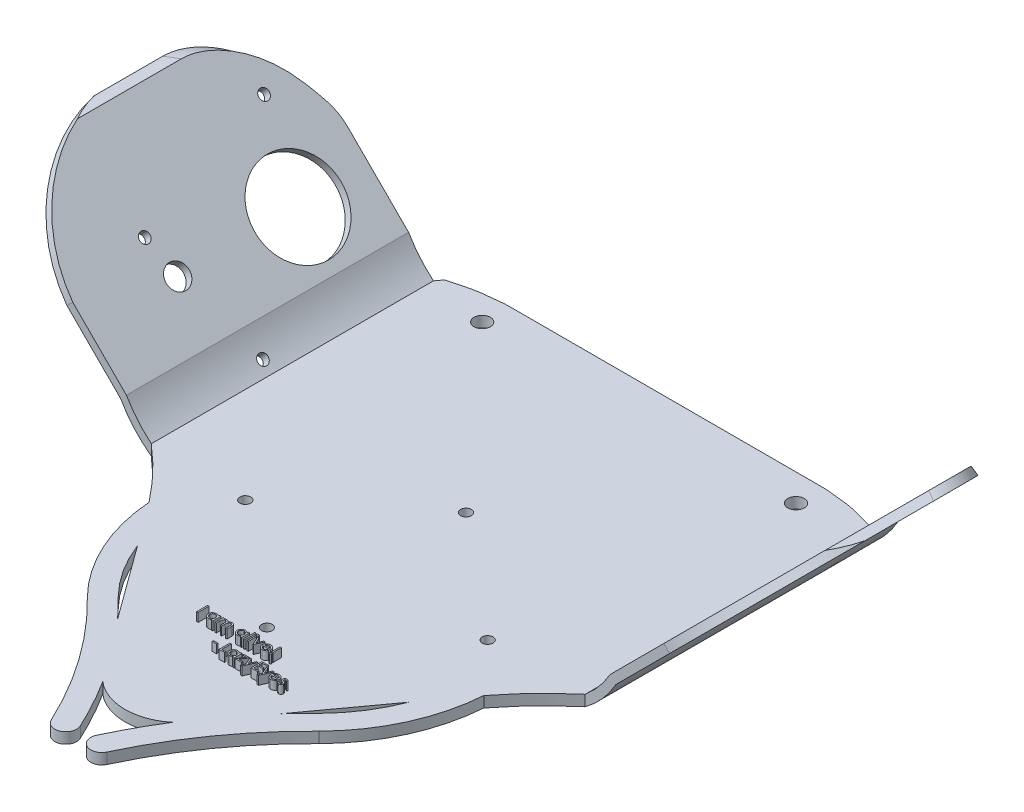
SolidWorks part; units mm, degrees
ref_plane "Front Plane" through (0, 0, 0) normal (0, 0, 1) x (1, 0, 0)
ref_plane "Top Plane" through (0, 0, 0) normal (0, 1, 0) x (1, 0, 0)
ref_plane "Right Plane" through (0, 0, 0) normal (1, 0, 0) x (0, 0, -1)
sketch "Sketch1" plane through (0, 0, 0) normal (0, 1, 0) x (1, 0, 0)
  line L0 (-53.9242, 189.7484) -> (-47.5742, 190.4453)
  line L1 (47.5742, 190.4453) -> (53.9242, 189.7484)
  line L2 (-63.6671, 185.8801) -> (-63.6671, 115.569)
  line L3 (63.6671, 185.8801) -> (63.6671, 115.569)
  line L4 (-63.6671, 115.569) -> (-63.6671, 103.057)
  line L5 (-62.2755, 187.7215) -> (-58.366, 188.769)
  line L6 (-63.6671, 185.8801) -> (-62.2755, 187.7215)
  line L7 (63.6671, 115.569) -> (63.6671, 103.057)
  line L8 (-45.218, 190.5) -> (45.218, 190.5)
  line L9 (63.6671, 185.8801) -> (62.2755, 187.7215)
  line L11 (-39.7923, 75.1534) -> (-23.9247, 53.3989)
  line L167 (39.7923, 75.1534) -> (23.9247, 53.3989)
  line L181 (62.2755, 187.7215) -> (58.366, 188.769)
  arc A1 (-10.307, 35.463) -> (10.307, 35.463) centre (0, 47.625) ccw
  arc A4 (-63.6671, 103.057) -> (-49.1129, 87.8559) centre (-129.382, 25.5708) cw
  arc A5 (-58.366, 188.769) -> (-53.9242, 189.7484) centre (-45.218, 139.7) cw
  arc A14 (23.9247, 53.3989) -> (29.4574, 59.1474) centre (120.746, -34.2501) cw
  arc A15 (34.0855, 54.7275) -> (33.9333, 54.5681) centre (31.6954, 56.8578) cw
  arc A16 (39.7923, 75.1534) -> (29.5378, 59.2233) centre (-3.4651, 91.7334) cw
  arc A17 (-47.5742, 190.4453) -> (-45.218, 190.5) centre (-45.218, 139.7) cw
  arc A18 (-2.3792, 20.9404) -> (-10.307, 35.463) centre (-120.746, -34.2501) ccw
  arc A19 (-8.1827, 18.2344) -> (-33.9333, 54.5681) centre (-120.746, -34.2501) ccw
  arc A20 (-8.1827, 18.2344) -> (-2.3792, 20.9404) centre (-5.2809, 19.5874) ccw
  arc A21 (-29.4574, 59.1474) -> (-29.5378, 59.2233) centre (-31.6954, 56.8578) ccw
  arc A23 (-49.1129, 87.8559) -> (-34.0855, 54.7275) centre (3.4651, 91.7334) ccw
  arc A24 (-39.7923, 75.1534) -> (-29.5378, 59.2233) centre (3.4651, 91.7334) ccw
  arc A25 (-34.0855, 54.7275) -> (-33.9333, 54.5681) centre (-31.6954, 56.8578) ccw
  arc A26 (-23.9247, 53.3989) -> (-29.4574, 59.1474) centre (-120.746, -34.2501) ccw
  arc A27 (49.1129, 87.8559) -> (34.0855, 54.7275) centre (-3.4651, 91.7334) cw
  arc A29 (29.4574, 59.1474) -> (29.5378, 59.2233) centre (31.6954, 56.8578) cw
  arc A31 (8.1827, 18.2344) -> (2.3792, 20.9404) centre (5.2809, 19.5874) cw
  arc A32 (8.1827, 18.2344) -> (33.9333, 54.5681) centre (120.746, -34.2501) cw
  arc A33 (2.3792, 20.9404) -> (10.307, 35.463) centre (120.746, -34.2501) cw
  arc A34 (47.5742, 190.4453) -> (45.218, 190.5) centre (45.218, 139.7) ccw
  arc A36 (58.366, 188.769) -> (53.9242, 189.7484) centre (45.218, 139.7) ccw
  arc A37 (63.6671, 103.057) -> (49.1129, 87.8559) centre (129.382, 25.5708) ccw
  point P28 (-51.906, 190.5)
  point P30 (-67.31, 186.3725)
  point P32 (0, 150.8125)
  point P50 (-16.804, 39.5041)
  point P55 (-40.3772, 68.7904)
  point P67 (0, 75.2413)
  point P69 (0, 150.7245)
  point P96 (0, 92.6888)
  point P151 (0, 168.7068)
  point P180 (-23.8506, 150.3045)
  point P235 (0, 131.9022)
  point P246 (53.9242, 150.7245)
  point P256 (40.3772, 68.7904)
  point P257 (16.804, 39.5041)
  point P258 (51.906, 190.5)
  dimension "D4" = 15.942
  dimension "D7" = 2.3792
  dimension "D8" = 50.8
  dimension "D9" = 3.4651
  dimension "D11" = 16.804
  dimension "D12" = 23.9247
  dimension "D13" = 40.3772
  dimension "D14" = 16.804
  dimension "D15" = 23.8506
  dimension "D17" = 39.5041
  dimension "D10" = 10.307
  dimension "D1" = 131.9022
  dimension "D16" = 40.3772
  dimension "D19" = 75.2413
  dimension "D23" = 139.7
  dimension "D18" = 68.7904
  dimension "D20" = 92.6888
  dimension "D21" = 150.3045
  dimension "D22" = 168.7068
extrude "Face" add sketch "Sketch1" along normal blind 3.175
sketch "Sketch2" plane through (0, 3.175, 0) normal (0, 1, 0) x (1, 0, 0)
  text T0 "<b>I am alive!</b>\r\n<b>        - LazyEyes</b>"
ref_plane "Plane1" through (0, 0, -185.8801) normal (0, 0, 1) x (1, 0, 0)
sketch "Sketch4" plane through (0, 0, -185.8801) normal (0, 0, 1) x (1, 0, 0)
  line L0 (-86.0332, 0) -> (86.1467, 0) construction
  line L1 (-113.0904, 50.5712) -> (-109.6939, 50.5712)
  line L2 (-72.6792, 10.16) -> (-113.0904, 50.5712)
  line L3 (-61.6244, 10.16) -> (-107.7333, 10.16) construction
  line L4 (-70.986, 11.8633) -> (-109.6939, 50.5712)
  line L6 (-53.9242, 3.175) -> (-58.366, 3.175) construction
  line L16 (-63.6671, 0) -> (-63.6671, 3.175)
  arc A0 (-72.6792, 10.16) -> (-63.6671, 0) centre (-44.776, 25.8337) ccw
  arc A1 (-70.986, 11.8633) -> (-63.6671, 3.175) centre (-43.2383, 27.8108) ccw
  dimension "D2" = 32.004
  dimension "D1" = 45
  dimension "D3" = 57.15
  dimension "D4" = 10.16
  dimension "D5" = 43.2383
  dimension "D6" = 44.776
  dimension "D7" = 70.986
extrude "Eyes" add sketch "Sketch4" along normal blind 82.804
ref_plane "Plane3" through (-31.2596, -31.2596, 0) normal (-0.7071, -0.7071, 0) x (0, 0, 1)
sketch "Sketch6" plane through (-31.2596, -31.2596, 0) normal (-0.7071, -0.7071, 0) x (0, 0, 1)
  line L0 (-185.8801, 115.7262) -> (-185.8801, 58.5762) construction
  line L1 (-103.0761, 115.7262) -> (-185.8801, 115.7262) construction
  line L3 (-168.4383, 115.7262) -> (-185.8801, 115.7262)
  line L4 (-185.8801, 115.7262) -> (-185.8801, 87.1512)
  arc A0 (-185.8801, 87.1512) -> (-168.4383, 115.7262) centre (-104.6851, 57.2016) cw
extrude "Cut-Extrude1" cut sketch "Sketch6" against normal blind 70.104
sketch "Sketch7" plane through (-31.2596, -31.2596, 0) normal (-0.7071, -0.7071, 0) x (0, 0, 1)
  line L0 (-135.7572, 115.7262) -> (-103.0761, 115.7262)
  line L1 (-103.0761, 115.7262) -> (-103.0761, 58.5762) construction
  line L2 (-103.0761, 115.7262) -> (-103.0761, 80.853)
  line L3 (-103.0761, 115.7262) -> (-168.4383, 115.7262) construction
  arc A0 (-135.7572, 115.7262) -> (-103.0761, 80.853) centre (-142.5038, 76.6536) cw
sketch "Sketch10" plane through (-31.2596, -31.2596, 0) normal (-0.7071, -0.7071, 0) x (0, 0, 1)
  line L0 (-164.7591, 74.5826) -> (-113.5646, 74.5826) construction
  circle A0 centre (-129.4531, 74.5826) radius 3.3976
  circle A1 centre (-164.7591, 74.5826) radius 12.7
  dimension "D2" = 25.4
  dimension "D1" = 35.306
extrude "Cut-Extrude3" cut sketch "Sketch10" against normal blind 70.104
sketch "Sketch11" plane through (0, 0, 0) normal (0, -1, 0) x (-1, 0, 0)
  line L0 (0, 31.683) -> (0, 190.5) construction
  line L1 (-45.218, 190.5) -> (45.218, 190.5) construction
  arc A0 (-10.307, 35.463) -> (10.307, 35.463) centre (0, 47.625) ccw construction
  circle A1 centre (46.0502, 182.5498) radius 2.413
  circle A2 centre (0, 131.7498) radius 1.5875
  circle A3 centre (35.56, 102.5398) radius 1.5875
  circle A4 centre (0, 73.3298) radius 1.5875
  circle A5 centre (-35.56, 102.5398) radius 1.5875
  circle A6 centre (-46.0502, 182.5498) radius 2.413
  dimension "D1" = 4.826
  dimension "D2" = 3.175
  dimension "D3" = 3.175
  dimension "D4" = 3.175
  dimension "D5" = 35.56
  dimension "D6" = 46.0502
  dimension "D7" = 7.9502
  dimension "D8" = 50.8
  dimension "D9" = 29.21
  dimension "D10" = 29.21
ref_plane "Plane4" through (0, 0, 0) normal (1, 0, 0) x (0, 0, -1)
extrude "Cut-Extrude13" cut sketch "Sketch7" against normal blind 70.104
fillet "Fillet10" radius 17.78 1 edges at (-111.406, 50.5712, -169.5115) type face fillet first side face at (-111.4764, 50.5712, -150.5316) second side face at (-101.9874, 41.163, -178.3306)
fillet "Fillet11" radius 17.78 1 edges at (-92.0357, 31.2147, -185.8801) type face fillet first side face at (-95.7969, 34.9737, -183.6075) second side face at (-76.0007, 14.4695, -185.8801)
mirror "Mirror3" about plane through (0, 0, 0) normal (1, 0, 0) of bodies 122
extrude "Boss-Extrude4" add sketch "Sketch2" along normal blind 2.54
ref_plane "Plane6" through (25.4, 0, 0) normal (1, 0, 0) x (0, 0, -1)
extrude "Cut-Extrude14" cut sketch "Sketch11" against normal through all
sketch "Sketch12" plane through (-31.2596, -31.2596, 0) normal (-0.7071, -0.7071, 0) x (0, 0, 1)
  line L0 (-171.5926, 109.5862) -> (-171.5926, 45.0194) construction
  line L1 (-185.8801, 83.7877) -> (-185.8801, 58.5762) construction
  line L2 (-127.1426, 113.2079) -> (-127.1426, 58.5762) construction
  line L3 (-103.0761, 58.5762) -> (-185.8801, 58.5762) construction
  line L4 (-185.8801, 45.0194) -> (-103.0761, 45.0194) construction
  line L5 (-138.4456, 115.7262) -> (-138.4456, 45.0194) construction
  line L6 (-135.7572, 115.7262) -> (-155.8385, 115.7262) construction
  arc A0 (-103.0761, 80.853) -> (-135.7572, 115.7262) centre (-142.5038, 76.6536) ccw construction
  circle A1 centre (-171.5926, 98.3316) radius 1.524
  circle A2 centre (-164.7591, 74.5826) radius 12.7 construction
  circle A3 centre (-138.4456, 50.8336) radius 1.524
  circle A4 centre (-127.1426, 84.9966) radius 1.524
  spline S0 degree 3 poles (-155.8385, 115.7262) (-157.1415, 115.7262) (-158.4199, 115.5848) (-160.3092, 115.2112) (-160.9343, 115.0593) (-162.1754, 114.7044) (-162.7939, 114.5005) (-164.6115, 113.8258) (-165.7778, 113.292) (-168.0324, 112.08) (-169.1205, 111.4016) (-170.6974, 110.2816) (-171.2151, 109.8899) (-172.222, 109.081) (-172.7118, 108.6633) (-174.1424, 107.372) (-175.0441, 106.4604) (-176.3215, 105.0195) (-176.7347, 104.5269) (-177.5357, 103.5169) (-177.9246, 102.998) (-179.0436, 101.4165) (-179.7262, 100.3301) (-180.3467, 99.2125) knots 0 0 0 0 0.125 0.125 0.1875 0.1875 0.25 0.25 0.375 0.375 0.5 0.5 0.5625 0.5625 0.625 0.625 0.75 0.75 0.8125 0.8125 0.875 0.875 1 1 1 1 construction
  dimension "D3" = 3.048
  dimension "D6" = 3.048
  dimension "D8" = 3.048
  dimension "D1" = 14.2875
  dimension "D2" = 44.45
  dimension "D4" = 23.749
  dimension "D5" = 33.147
  dimension "D7" = 23.749
  dimension "D9" = 10.414
extrude "Cut-Extrude15" cut sketch "Sketch12" against normal through all both and the other way through all
sketch "Sketch13" plane through (31.2596, -31.2596, 0) normal (0.7071, -0.7071, 0) x (0, 0, -1)
  line L0 (127.1426, 113.2079) -> (127.1426, 45.0194) construction
  line L1 (171.5926, 109.5862) -> (171.5926, 45.0194) construction
  line L2 (138.4456, 115.7262) -> (138.4456, 45.0194) construction
  line L3 (185.8801, 83.7877) -> (185.8801, 58.5762) construction
  line L4 (185.8801, 45.0194) -> (103.0761, 45.0194) construction
  line L5 (135.7572, 115.7262) -> (155.8385, 115.7262) construction
  circle A0 centre (127.1426, 64.1686) radius 1.524
  circle A1 centre (138.4456, 98.3316) radius 1.524
  circle A2 centre (171.5926, 50.8336) radius 1.524
  circle A3 centre (164.7591, 74.5826) radius 12.7 construction
  arc A4 (135.7572, 115.7262) -> (103.0761, 80.853) centre (142.5038, 76.6536) ccw construction
  spline S0 degree 3 poles (155.8385, 115.7262) (157.1415, 115.7262) (158.4199, 115.5848) (160.3092, 115.2112) (160.9343, 115.0593) (162.1754, 114.7044) (162.7939, 114.5005) (164.6115, 113.8258) (165.7778, 113.292) (168.0324, 112.08) (169.1205, 111.4016) (170.6974, 110.2816) (171.2151, 109.8899) (172.222, 109.081) (172.7118, 108.6633) (174.1424, 107.372) (175.0441, 106.4604) (176.3215, 105.0195) (176.7347, 104.5269) (177.5357, 103.5169) (177.9246, 102.998) (179.0436, 101.4165) (179.7262, 100.3301) (180.3467, 99.2125) knots 0 0 0 0 0.125 0.125 0.1875 0.1875 0.25 0.25 0.375 0.375 0.5 0.5 0.5625 0.5625 0.625 0.625 0.75 0.75 0.8125 0.8125 0.875 0.875 1 1 1 1 construction
  point P16 (171.5926, 109.5862)
  point P19 (171.5926, 45.0194)
  point P22 (160.2896, 45.0194)
  point P23 (127.1426, 45.0194)
  point P24 (127.1426, 113.2079)
  point P28 (0, 0)
  point P29 (138.4456, 115.7262)
  point P32 (127.1426, 48.2296)
  point P33 (127.1426, 45.0194)
  dimension "D2" = 3.048
  dimension "D4" = 3.048
  dimension "D5" = 3.048
  dimension "D7" = 23.749
  dimension "D1" = 44.45
  dimension "D3" = 33.147
  dimension "D6" = 14.2875
  dimension "D8" = 23.749
  dimension "D9" = 10.414
extrude "Cut-Extrude16" cut sketch "Sketch13" against normal through all both and the other way through all
